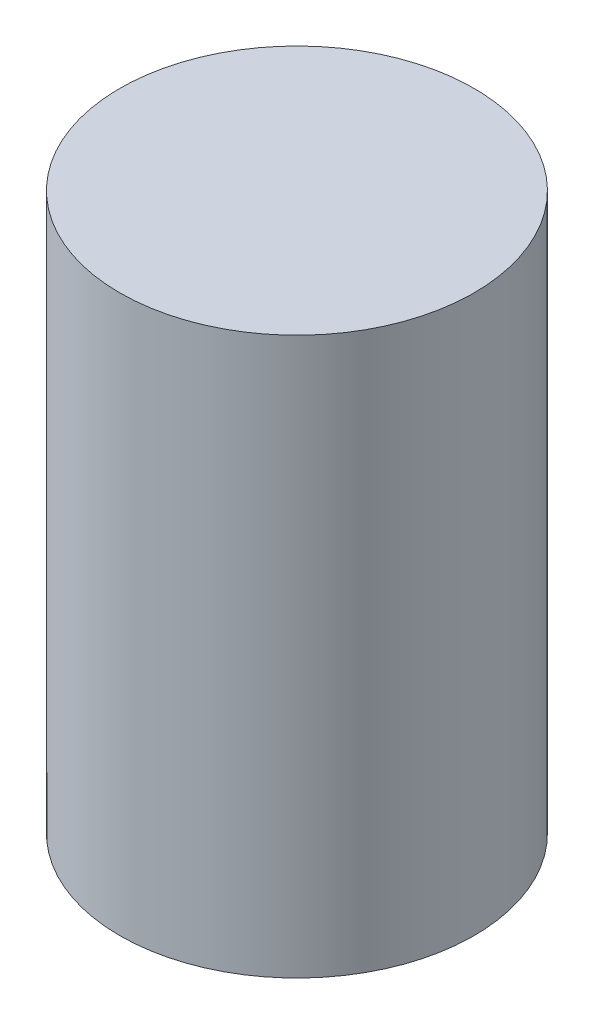
SolidWorks part; units mm, degrees
ref_plane "Front Plane" through (0, 0, 0) normal (0, 0, 1) x (1, 0, 0)
ref_plane "Top Plane" through (0, 0, 0) normal (0, 1, 0) x (1, 0, 0)
ref_plane "Right Plane" through (0, 0, 0) normal (1, 0, 0) x (0, 0, -1)
sketch "Sketch1" plane through (0, 0, 0) normal (0, 1, 0) x (1, 0, 0)
  circle A0 centre (0, 0) radius 17.5
  dimension "D1" = 35
extrude "Boss-Extrude1" add sketch "Sketch1" along normal blind 55
ref_axis "Axis1" through (0, 55, 0) along (0, -1, 0)
